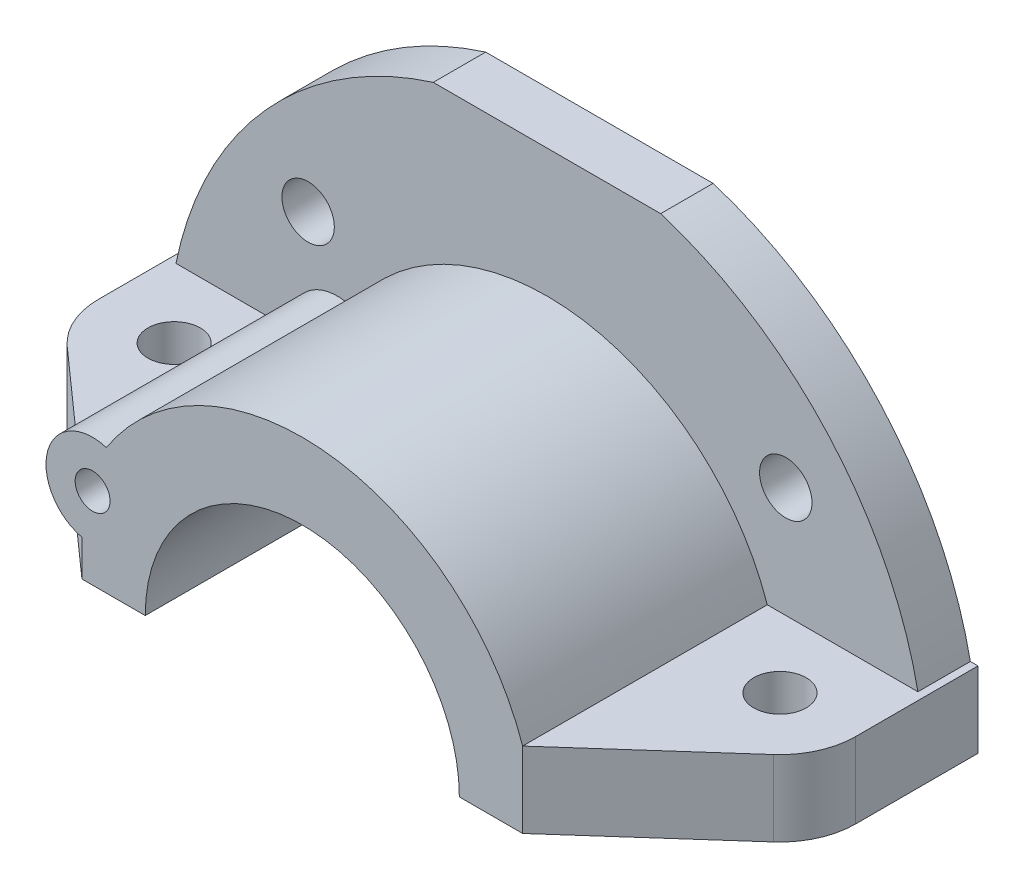
SolidWorks part; units mm, degrees
ref_plane "Front Plane" through (0, 0, 0) normal (0, 0, 1) x (1, 0, 0)
ref_plane "Top Plane" through (0, 0, 0) normal (0, 1, 0) x (1, 0, 0)
ref_plane "Right Plane" through (0, 0, 0) normal (1, 0, 0) x (0, 0, -1)
sketch "Sketch1" plane through (0, 0, 0) normal (0, 0, 1) x (1, 0, 0)
  line L0 (0, 0) -> (-37527.0458, 0) construction
  line L1 (0, 0) -> (0, -37527.0458) construction
  line L2 (-65, 0) -> (65, 0)
  line L3 (-63.6867, 13) -> (-37.8286, 13)
  line L4 (37.8286, 13) -> (63.6867, 13)
  line L5 (-19.5192, 62) -> (19.5192, 62)
  line L6 (63.6867, 13) -> (65, 13)
  line L7 (65, 0) -> (65, 13)
  line L8 (-65, 0) -> (-65, 13)
  line L9 (-63.6867, 13) -> (-65, 13)
  arc A0 (26.9625, 0) -> (-26.9625, 0) centre (0, 0) ccw
  arc A1 (40, 0) -> (-33.6386, 21.6436) centre (0, 0) ccw
  arc A2 (63.6867, 13) -> (19.5192, 62) centre (0, 0) ccw
  arc A3 (-19.5192, 62) -> (-63.6867, 13) centre (0, 0) ccw
  circle A4 centre (41, 32) radius 4.5
  circle A5 centre (-41, 32) radius 4.5
  arc A8 (-33.6386, 21.6436) -> (-40, 0) centre (0, 0) ccw
  point P7 (-33.6386, 21.1971)
  point P22 (-37.8286, 13)
  dimension "D1" = 40
  dimension "D2" = 65
  dimension "D3" = 53.925
  dimension "D6" = 32
  dimension "D8" = 9
  dimension "D4" = 13
  dimension "D5" = 62
  dimension "D7" = 82
  dimension "D9" = 130
extrude "Boss-Extrude1" add sketch "Sketch1" along normal blind 9 contours L5 A3 L3 A1 L4 A2 A4 A5 region at (-50.7576, 14.3647, 0)
extrude "Boss-Extrude2" add sketch "Sketch1<3>" along normal blind 51 contours L2 A1 A0 | L3 A3 L2 A1 | L2 A2 L4 A1 region at (-52.134, 6.591, 0) region at (-38.5712, 6.4427, 0) region at (52.134, 6.591, 0)
sketch "Sketch1<3>" plane through (0, 0, 0) normal (0, 0, 1) x (1, 0, 0) same geometry as "Sketch1"
sketch "Sketch2" plane through (0, 13, 0) normal (0, 1, 0) x (1, 0, 0)
  line L0 (0, -55) -> (0, 55) construction
  line L1 (63.6867, 0) -> (19.5192, 0) construction
  line L2 (37.8286, -51) -> (60.639, -30.7143)
  line L3 (37.8286, -51) -> (65, -51)
  line L5 (65, -51) -> (65, -21)
  line L6 (65, -21) -> (95.3262, -43.4401)
  line L7 (-37.8286, -51) -> (-65, -51)
  line L8 (-37.8286, -51) -> (-60.639, -30.7143)
  line L9 (-65, -51) -> (-65, -21)
  circle A0 centre (52, -21) radius 4.5
  circle A1 centre (-52, -21) radius 4.5
  arc A2 (60.639, -30.7143) -> (65, -21) centre (52, -21) ccw
  arc A3 (-60.639, -30.7143) -> (-65, -21) centre (-52, -21) cw
  line M4 (37.8286, -51) -> (65, -51)
  line M6 (65, -51) -> (65, 0)
  dimension "D1" = 21
  dimension "D3" = 9
  dimension "D4" = 26
  dimension "D2" = 52
extrude "Cut-Extrude1" cut sketch "Sketch2" against normal blind 51 contours L8 A3 L9 L7 | A1 | A2 L2 M4 M6 | A0 region at (56.0545, 13, 42.7192) region at (-56.0545, 13, 42.7192) region at (52, 13, 21) region at (-52, 13, 21)
sketch "Sketch3" plane through (0, 0, 51) normal (0, 0, 1) x (1, 0, 0)
  line L0 (-37.8286, 0) -> (-60.639, 0) construction
  circle A0 centre (-36, 14) radius 3
  circle A1 centre (-36, 14) radius 8
  point P3 (0, 0)
  arc M5 (37.8286, 13) -> (-37.8286, 13) centre (0, 0) ccw
  line M6 (-37.8286, 13) -> (-37.8286, 0)
  dimension "D1" = 36
  dimension "D3" = 16
  dimension "D4" = 6
  dimension "D2" = 14
extrude "Boss-Extrude4" add sketch "Sketch3" against normal blind 51 contours A1 A0 M6 M5 | A1 A0 M5 M6 | A0 M6 M5 | A0 M5 M6 region at (-35.4246, 13.8055, 51) region at (-32.5697, 13.0694, 51) region at (-37.8889, 14.6386, 51) region at (-39.7743, 15.0239, 51)
extrude "Cut-Extrude2" cut sketch "Sketch3<3>" against normal blind 13 contours A0 M6 M5 | A0 M5 M6 region at (-35.4246, 13.8055, 51) region at (-37.8889, 14.6386, 51)
sketch "Sketch3<3>" plane through (0, 0, 51) normal (0, 0, 1) x (1, 0, 0) same geometry as "Sketch3"
